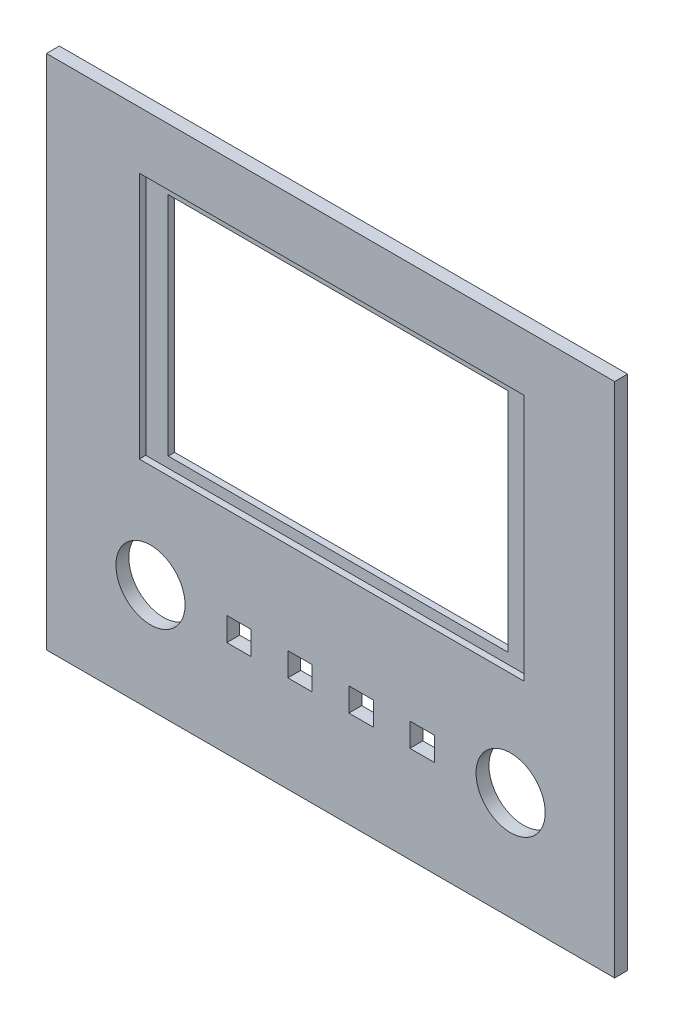
SolidWorks part; units mm, degrees
ref_plane "Front Plane" through (0, 0, 0) normal (0, 0, 1) x (1, 0, 0)
ref_plane "Top Plane" through (0, 0, 0) normal (0, 1, 0) x (1, 0, 0)
ref_plane "Right Plane" through (0, 0, 0) normal (1, 0, 0) x (0, 0, -1)
sketch "Sketch1" plane through (0, 0, 0) normal (0, 0, 1) x (1, 0, 0)
  line L0 (-10.7655, -52.97) -> (-10.7655, -58.77)
  line L1 (-41.76, -27.84) -> (41.76, -27.84)
  line L2 (-41.76, -27.84) -> (-41.76, 27.84)
  line L3 (-41.76, 27.84) -> (41.76, 27.84)
  line L4 (41.76, -27.84) -> (41.76, 27.84)
  line L5 (-41.76, -27.84) -> (41.76, 27.84) construction
  line L6 (-41.76, 27.84) -> (41.76, -27.84) construction
  line L7 (-70.1155, 44.4994) -> (69.5845, 44.4994)
  line L8 (-70.1155, 44.4994) -> (-70.1155, -82.5006)
  line L9 (-70.1155, -82.5006) -> (69.5845, -82.5006)
  line L10 (69.5845, 44.4994) -> (69.5845, -82.5006)
  line L11 (-25.7655, -52.97) -> (-19.7655, -52.97)
  line L12 (-25.7655, -52.97) -> (-25.7655, -58.77)
  line L13 (-25.7655, -58.77) -> (-19.7655, -58.77)
  line L14 (-19.7655, -52.97) -> (-19.7655, -58.77)
  line L15 (44.0042, -55.87) -> (-44.5351, -55.87) construction
  line L16 (-10.7655, -52.97) -> (-4.7655, -52.97)
  line L17 (-4.7655, -52.97) -> (-4.7655, -58.77)
  line L18 (-10.7655, -58.77) -> (-4.7655, -58.77)
  line L19 (4.2345, -52.97) -> (4.2345, -58.77)
  line L20 (4.2345, -52.97) -> (10.2345, -52.97)
  line L21 (10.2345, -52.97) -> (10.2345, -58.77)
  line L22 (4.2345, -58.77) -> (10.2345, -58.77)
  line L23 (19.2345, -52.97) -> (19.2345, -58.77)
  line L24 (19.2345, -52.97) -> (25.2345, -52.97)
  line L25 (25.2345, -52.97) -> (25.2345, -58.77)
  line L26 (19.2345, -58.77) -> (25.2345, -58.77)
  line L27 (-4.7655, -55.87) -> (4.2345, -55.87) construction
  line L29 (-4.7655, -55.87) -> (4.2345, -55.87) construction
  line L30 (-70.1155, -19.0006) -> (-58.5356, -19.0006) construction
  line L31 (58.0047, -19.0006) -> (69.5845, -19.0006) construction
  line L32 (-0.2655, -82.5006) -> (-0.2655, -69.8704) construction
  line L33 (-0.2655, 44.4994) -> (-0.2655, 31.8693) construction
  line L34 (-58.5356, 31.8693) -> (-58.5356, -69.8704)
  line L35 (58.0047, 31.8693) -> (-58.5356, 31.8693)
  line L36 (58.0047, -69.8704) -> (58.0047, 31.8693)
  line L37 (-58.5356, -69.8704) -> (58.0047, -69.8704)
  line L38 (-58.5356, 31.8693) -> (-58.5356, -69.8704)
  line L39 (58.0047, 31.8693) -> (-58.5356, 31.8693)
  line L40 (58.0047, -69.8704) -> (58.0047, 31.8693)
  line L41 (-58.5356, -69.8704) -> (58.0047, -69.8704)
  circle A0 centre (44.0042, -55.87) radius 8.5
  circle A1 centre (-44.5351, -55.87) radius 8.5
  point P0 (0, 0)
  point P16 (-25.7655, -55.87)
  dimension "D12" = 17
  dimension "D13" = 17
  dimension "D1" = 55.68
  dimension "D2" = 83.52
  dimension "D3" = 139.7
  dimension "D4" = 127
  dimension "D5" = 0
  dimension "D6" = 14.0005
  dimension "D7" = 14.0005
  dimension "D8" = 14.0005
  dimension "D9" = 14.0005
  dimension "D14" = 6
  dimension "D15" = 5.8
  dimension "D16" = 4
extrude "Boss-Extrude1" add sketch "Sketch1" along normal blind 3.175 contours L9 L8 | A1 A0 L11 L14 L13 L12 L4 L1 L2 L3 L18 L0 L16 L17 L22 L19 L20 L21 L26 L23 L24 L25 | L9 L10 L7 L8 | L9 L8 region at (-0.2655, 42.6114, 0) region at (-0.4521, -29.0548, 0)
sketch "Sketch2" plane through (0, 0, 3.175) normal (0, 0, 1) x (1, 0, 0)
  line L0 (41.76, -27.84) -> (41.76, 27.84) construction
  line L1 (-41.76, -27.84) -> (41.76, -27.84) construction
  line L2 (-41.76, -27.84) -> (-41.76, 27.84) construction
  line L3 (-41.76, 27.84) -> (41.76, 27.84) construction
  line L4 (41.76, -27.84) -> (41.76, 27.84)
  line L5 (-41.76, -27.84) -> (41.76, -27.84)
  line L6 (-41.76, -27.84) -> (-41.76, 27.84)
  line L7 (-41.76, 27.84) -> (41.76, 27.84)
  line L9 (47.285, 30.44) -> (-47.285, 30.44)
  line L10 (47.285, 30.44) -> (47.285, -30.44)
  line L11 (47.285, -30.44) -> (-47.285, -30.44)
  line L12 (-47.285, 30.44) -> (-47.285, -30.44)
  line L13 (47.285, 30.44) -> (-47.285, -30.44) construction
  line L14 (47.285, -30.44) -> (-47.285, 30.44) construction
  point P3 (0, 0)
  dimension "D1" = 94.57
  dimension "D2" = 60.88
extrude "Cut-Extrude1" cut sketch "Sketch2" against normal blind 1.5875
